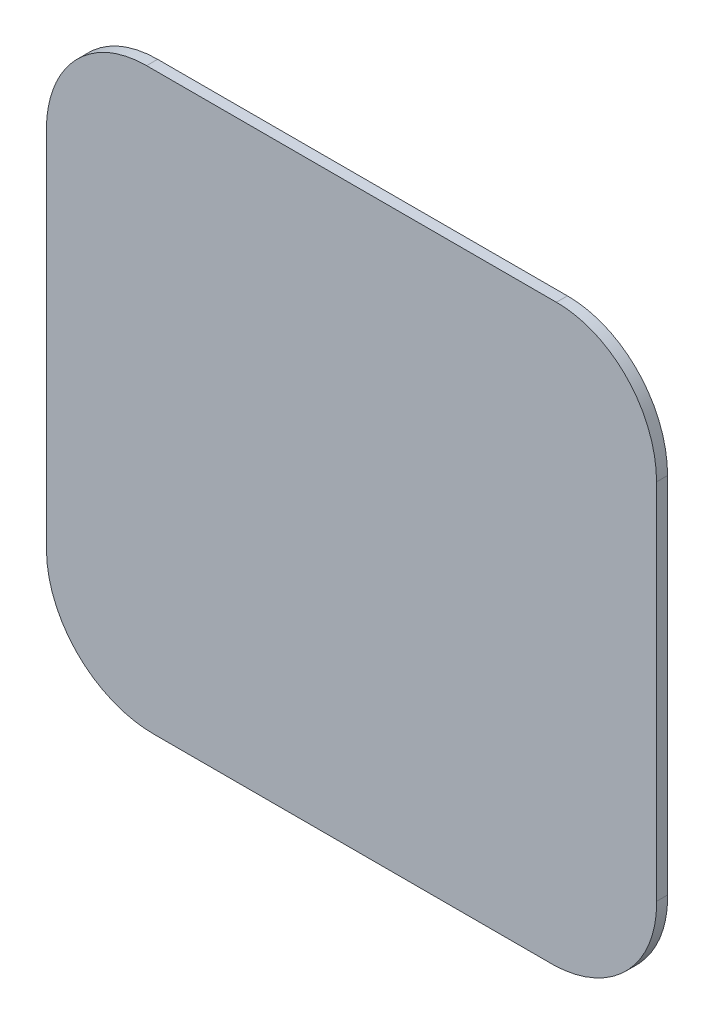
SolidWorks part; units mm, degrees
material "Beech"
ref_plane "Front Plane" through (0, 0, 0) normal (0, 0, 1) x (1, 0, 0)
ref_plane "Top Plane" through (0, 0, 0) normal (0, 1, 0) x (1, 0, 0)
ref_plane "Right Plane" through (0, 0, 0) normal (1, 0, 0) x (0, 0, -1)
sketch "Sketch1" plane through (0, 0, 0) normal (0, 0, 1) x (1, 0, 0)
  line L0 (-105.3184, 124.9067) -> (-105.3184, -72.5)
  line L1 (-105.3184, -72.5) -> (103.4563, -72.5)
  line L2 (103.4563, -72.5) -> (103.4563, 124.9067)
  line L3 (103.4563, 124.9067) -> (-105.3184, 124.9067)
  line L4 (-80, 72.5) -> (-80, -72.5)
  line L5 (-80, -72.5) -> (80, -72.5)
  line L6 (80, -72.5) -> (80, 72.5)
  line L7 (80, 72.5) -> (-80, 72.5)
  line L8 (-80, 72.5) -> (-80, -72.5) construction
  line L9 (-80, -72.5) -> (80, -72.5) construction
  line L10 (80, -72.5) -> (80, 72.5) construction
  point P25 (-25, 60.7089)
  dimension "D1" = 0
extrude "Boss-Extrude1" add sketch "Sketch1" along normal blind 3
sketch3d "3DSketch1"
  line L0 (-83, -42.5, 2.9036) -> (-83, 56.327, 2.9036)
  line L1 (-83, -42.5, 2.9036) -> (-83, 56.327, 2.9036)
  line L2 (55.7409, 85.0317, 3) -> (-55.7409, 85.0317, 3)
  line L3 (55.7409, 85.0317, 3) -> (-55.7409, 85.0317, 3)
  line L4 (83, 56.327, 2.9036) -> (83, -42.5, 2.9036)
  line L5 (83, 56.327, 2.9036) -> (83, -42.5, 2.9036)
  line L7 (-57.4005, -70.3847, 3) -> (54.8473, -71.5, 2.965)
  spline S0 degree 3 poles (845.7378, -314.4009, 3.5223) (143.8658, -123.3345, 2.8787) (-95.3665, -9.6791, 2.7552) (-82.3503, 62.6938, 2.9171) (-82.1487, 63.5851, 2.9192) (-81.784, 64.9117, 2.9223) (-81.6521, 65.3522, 2.9234) (-81.367, 66.2295, 2.9256) (-81.2136, 66.667, 2.9266) (-80.4005, 68.822, 2.9321) (-79.5995, 70.4619, 2.9365) (-78.1712, 72.7951, 2.9432) (-77.657, 73.5515, 2.9454) (-76.5492, 75.02, 2.9499) (-75.9532, 75.7339, 2.9522) (-74.0842, 77.7574, 2.9589) (-72.7199, 78.9671, 2.9633) (-70.4933, 80.5694, 2.9697) (-69.7201, 81.0683, 2.9718) (-68.1133, 81.9895, 2.976) (-67.2931, 82.4042, 2.978) (-64.7838, 83.5145, 2.9838) (-63.0463, 84.0777, 2.9875) (-60.7916, 84.5546, 2.9917) (-60.3354, 84.6387, 2.9925) (-59.4217, 84.7823, 2.9942) (-58.9638, 84.842, 2.9949) (15.669, 92.5958, 3.1188) (114.6789, -213.0937, 2.6588) (241.5021, -869.7537, 1.5457) knots -4.849351 -4.849351 -4.849351 -4.849351 0.125 0.125 0.1875 0.1875 0.21875 0.21875 0.25 0.25 0.375 0.375 0.4375 0.4375 0.5 0.5 0.625 0.625 0.6875 0.6875 0.75 0.75 0.875 0.875 0.90625 0.90625 0.9375 0.9375 5.989732 5.989732 5.989732 5.989732 only from (-83, 56.327, 2.9036) to (-55.7409, 85.0317, 3)
  spline S1 degree 3 poles (-83, 56.327, 2.9036) (-82.9987, 58.1769, 2.9073) (-82.8348, 59.9997, 2.9111) (-82.3503, 62.6938, 2.9171) (-82.1487, 63.5851, 2.9192) (-81.784, 64.9117, 2.9223) (-81.6521, 65.3522, 2.9234) (-81.367, 66.2295, 2.9256) (-81.2136, 66.667, 2.9266) (-80.4005, 68.822, 2.9321) (-79.5995, 70.4619, 2.9365) (-78.1712, 72.7951, 2.9432) (-77.657, 73.5515, 2.9454) (-76.5492, 75.02, 2.9499) (-75.9532, 75.7339, 2.9522) (-74.0842, 77.7574, 2.9589) (-72.7199, 78.9671, 2.9633) (-70.4933, 80.5694, 2.9697) (-69.7201, 81.0683, 2.9718) (-68.1133, 81.9895, 2.976) (-67.2931, 82.4042, 2.978) (-64.7838, 83.5145, 2.9838) (-63.0463, 84.0777, 2.9875) (-60.7916, 84.5546, 2.9917) (-60.3354, 84.6387, 2.9925) (-59.4217, 84.7823, 2.9942) (-58.9638, 84.842, 2.9949) (-57.5875, 84.985, 2.9972) (-56.6661, 85.0324, 2.9987) (-55.7409, 85.0317, 3) knots 0 0 0 0 0.125 0.125 0.1875 0.1875 0.21875 0.21875 0.25 0.25 0.375 0.375 0.4375 0.4375 0.5 0.5 0.625 0.625 0.6875 0.6875 0.75 0.75 0.875 0.875 0.90625 0.90625 0.9375 0.9375 1 1 1 1
  spline S2 degree 3 poles (-289.6468, -853.4257, 2.481) (-113.5107, -151.129, 3.0446) (-6.1225, 98.5754, 3.1498) (62.0878, 84.2822, 2.9855) (62.9752, 84.0478, 2.9833) (64.7352, 83.482, 2.9788) (65.5969, 83.1537, 2.9765) (68.1083, 82.0454, 2.9697) (69.694, 81.1399, 2.9651) (71.5651, 79.7991, 2.9593) (71.9348, 79.5196, 2.9582) (72.6565, 78.9442, 2.9559) (73.0086, 78.6483, 2.9547) (74.0393, 77.7369, 2.9513) (75.3458, 76.4581, 2.9468) (76.5201, 75.0559, 2.9424) (77.6284, 73.592, 2.9381) (78.1517, 72.8251, 2.936) (79.5948, 70.473, 2.9298) (80.3956, 68.831, 2.9259) (81.3669, 66.2625, 2.9204) (81.6523, 65.3878, 2.9186) (82.1438, 63.606, 2.9152) (82.3472, 62.7093, 2.9135) (96.6275, -16.5223, 2.7772) (-193.7163, -136.4345, 3.235) (-848.9704, -306.1858, 4.4029) knots -4.578436 -4.578436 -4.578436 -4.578436 0.125 0.125 0.1875 0.1875 0.25 0.25 0.375 0.375 0.40625 0.40625 0.4375 0.4375 0.5 0.5625 0.5625 0.625 0.625 0.75 0.75 0.8125 0.8125 0.875 0.875 6.300815 6.300815 6.300815 6.300815 only from (55.7409, 85.0317, 3) to (83, 56.327, 2.9036)
  spline S3 degree 3 poles (55.7409, 85.0317, 3) (57.587, 85.033, 2.9961) (59.4043, 84.8445, 2.992) (62.0878, 84.2822, 2.9855) (62.9752, 84.0478, 2.9833) (64.7352, 83.482, 2.9788) (65.5969, 83.1537, 2.9765) (68.1083, 82.0454, 2.9697) (69.694, 81.1399, 2.9651) (71.5651, 79.7991, 2.9593) (71.9348, 79.5196, 2.9582) (72.6565, 78.9442, 2.9559) (73.0086, 78.6483, 2.9547) (74.0393, 77.7369, 2.9513) (75.3458, 76.4581, 2.9468) (76.5201, 75.0559, 2.9424) (77.6284, 73.592, 2.9381) (78.1517, 72.8251, 2.936) (79.5948, 70.473, 2.9298) (80.3956, 68.831, 2.9259) (81.3669, 66.2625, 2.9204) (81.6523, 65.3878, 2.9186) (82.1438, 63.606, 2.9152) (82.3472, 62.7093, 2.9135) (82.835, 60.0024, 2.9089) (82.9987, 58.1758, 2.9061) (83, 56.327, 2.9036) knots 0 0 0 0 0.125 0.125 0.1875 0.1875 0.25 0.25 0.375 0.375 0.40625 0.40625 0.4375 0.4375 0.5 0.5625 0.5625 0.625 0.625 0.75 0.75 0.8125 0.8125 0.875 0.875 1 1 1 1
  spline S4 degree 3 poles (-859.369, 292.0653, 3.8986) (-111.276, 112.4573, 3.039) (94.1422, 15.6372, 2.8415) (82.379, -48.9917, 2.9097) (82.1672, -49.9003, 2.9107) (81.6513, -51.7035, 2.9129) (81.3458, -52.6, 2.914) (80.3098, -55.2097, 2.9175) (79.4565, -56.863, 2.92) (78.1883, -58.8226, 2.9233) (77.9245, -59.2091, 2.924) (77.3763, -59.9711, 2.9253) (77.091, -60.3477, 2.926) (76.2109, -61.4513, 2.9281) (75.5923, -62.1525, 2.9295) (73.6439, -64.156, 2.9337) (72.2222, -65.3588, 2.9366) (70.2881, -66.6925, 2.9403) (69.8925, -66.9512, 2.9411) (69.0933, -67.446, 2.9425) (68.6891, -67.6828, 2.9433) (67.4627, -68.3614, 2.9455) (65.791, -69.1824, 2.9484) (64.0474, -69.838, 2.9512) (62.7124, -70.267, 2.9534) (62.2628, -70.3994, 2.9541) (61.3544, -70.643, 2.9555) (60.8951, -70.7542, 2.9562) (-14.1598, -86.9814, 3.0702) (-127.8298, 195.8272, 2.9937) (-292.1789, 866.3485, 2.6708) knots -4.224634 -4.224634 -4.224634 -4.224634 0.125 0.125 0.1875 0.1875 0.25 0.25 0.375 0.375 0.40625 0.40625 0.4375 0.4375 0.5 0.5 0.625 0.625 0.65625 0.65625 0.6875 0.6875 0.75 0.8125 0.8125 0.84375 0.84375 0.875 0.875 5.945598 5.945598 5.945598 5.945598 only from (83, -42.5, 2.9036) to (54.8473, -71.5, 2.965)
  spline S5 degree 3 poles (83, -42.5, 2.9036) (83.0329, -44.3869, 2.9051) (82.8789, -46.2452, 2.9068) (82.379, -48.9917, 2.9097) (82.1672, -49.9003, 2.9107) (81.6513, -51.7035, 2.9129) (81.3458, -52.6, 2.914) (80.3098, -55.2097, 2.9175) (79.4565, -56.863, 2.92) (78.1883, -58.8226, 2.9233) (77.9245, -59.2091, 2.924) (77.3763, -59.9711, 2.9253) (77.091, -60.3477, 2.926) (76.2109, -61.4513, 2.9281) (75.5923, -62.1525, 2.9295) (73.6439, -64.156, 2.9337) (72.2222, -65.3588, 2.9366) (70.2881, -66.6925, 2.9403) (69.8925, -66.9512, 2.9411) (69.0933, -67.446, 2.9425) (68.6891, -67.6828, 2.9433) (67.4627, -68.3614, 2.9455) (65.791, -69.1824, 2.9484) (64.0474, -69.838, 2.9512) (62.7124, -70.267, 2.9534) (62.2628, -70.3994, 2.9541) (61.3544, -70.643, 2.9555) (60.8951, -70.7542, 2.9562) (58.5965, -71.2512, 2.9597) (56.7338, -71.4671, 2.9624) (54.8473, -71.5, 2.965) knots 0 0 0 0 0.125 0.125 0.1875 0.1875 0.25 0.25 0.375 0.375 0.40625 0.40625 0.4375 0.4375 0.5 0.5 0.625 0.625 0.65625 0.65625 0.6875 0.6875 0.75 0.8125 0.8125 0.84375 0.84375 0.875 0.875 1 1 1 1
  spline S6 degree 3 poles (854.0596, 306.6892, 3) (108.2999, 114.5623, 3) (-95.0277, 14.8956, 3) (-82.2695, -48.8652, 3) (-82.0459, -49.754, 3) (-81.5083, -51.5161, 3) (-81.1929, -52.3914, 3) (-80.1307, -54.9368, 3) (-79.2642, -56.5459, 3) (-77.9851, -58.4488, 3) (-77.7194, -58.8239, 3) (-77.1679, -59.5629, 3) (-76.8813, -59.9279, 3) (-75.998, -60.9967, 3) (-75.3784, -61.6748, 3) (-73.4304, -63.6091, 3) (-72.0135, -64.7661, 3) (-70.0911, -66.0429, 3) (-69.6981, -66.2902, 3) (-68.9047, -66.7625, 3) (-68.5036, -66.9881, 3) (-67.2875, -67.6336, 3) (-65.6316, -68.4113, 3) (-63.9079, -69.0253, 3) (-62.5893, -69.4237, 3) (-62.1455, -69.5461, 3) (-61.2491, -69.7698, 3) (-60.7962, -69.8711, 3) (13.8382, -84.6496, 3) (121.8565, 200.0841, 3) (273.8484, 873.9357, 3) knots -4.258592 -4.258592 -4.258592 -4.258592 0.125 0.125 0.1875 0.1875 0.25 0.25 0.375 0.375 0.40625 0.40625 0.4375 0.4375 0.5 0.5 0.625 0.625 0.65625 0.65625 0.6875 0.6875 0.75 0.8125 0.8125 0.84375 0.84375 0.875 0.875 5.989794 5.989794 5.989794 5.989794 only from (-82.9907, -42.5, 3) to (-54.8435, -70.5, 3)
  spline S7 degree 3 poles (-82.9907, -42.5, 3) (-82.9907, -44.3537, 3) (-82.8075, -46.1763, 3) (-82.2695, -48.8652, 3) (-82.0459, -49.754, 3) (-81.5083, -51.5161, 3) (-81.1929, -52.3914, 3) (-80.1307, -54.9368, 3) (-79.2642, -56.5459, 3) (-77.9851, -58.4488, 3) (-77.7194, -58.8239, 3) (-77.1679, -59.5629, 3) (-76.8813, -59.9279, 3) (-75.998, -60.9967, 3) (-75.3784, -61.6748, 3) (-73.4304, -63.6091, 3) (-72.0135, -64.7661, 3) (-70.0911, -66.0429, 3) (-69.6981, -66.2902, 3) (-68.9047, -66.7625, 3) (-68.5036, -66.9881, 3) (-67.2875, -67.6336, 3) (-65.6316, -68.4113, 3) (-63.9079, -69.0253, 3) (-62.5893, -69.4237, 3) (-62.1455, -69.5461, 3) (-61.2491, -69.7698, 3) (-60.7962, -69.8711, 3) (-59.368, -70.1539, 3) (-58.3872, -70.2953, 3) (-57.4005, -70.3847, 3) knots 0 0 0 0 0.125 0.125 0.1875 0.1875 0.25 0.25 0.375 0.375 0.40625 0.40625 0.4375 0.4375 0.5 0.5 0.625 0.625 0.65625 0.65625 0.6875 0.6875 0.75 0.8125 0.8125 0.84375 0.84375 0.875 0.875 0.942224 0.942224 0.942224 0.942224
sketch "Sketch3" plane through (0, 0, 3) normal (0, 0, 1) x (1, 0, 0)
  line L0 (-83, -42.5) -> (-83, 56.327) construction
  line L1 (83, 56.327) -> (83, -42.5) construction
  line L2 (55.7409, 85.0317) -> (-55.7409, 85.0317) construction
  line L3 (-83, -42.5) -> (-83, 56.327)
  line L4 (83, 56.327) -> (83, -42.5)
  line L5 (55.7409, 85.0317) -> (-55.7409, 85.0317)
  line L6 (-53.847, -71.5) -> (54.8473, -71.5)
  spline S0 degree 3 poles (-859.369, 292.0653) (-111.276, 112.4573) (94.1422, 15.6372) (82.379, -48.9917) (82.1672, -49.9003) (81.6513, -51.7035) (81.3458, -52.6) (80.3098, -55.2097) (79.4565, -56.863) (78.1883, -58.8226) (77.9245, -59.2091) (77.3763, -59.9711) (77.091, -60.3477) (76.2109, -61.4513) (75.5923, -62.1525) (73.6439, -64.156) (72.2222, -65.3588) (70.2881, -66.6925) (69.8925, -66.9512) (69.0933, -67.446) (68.6891, -67.6828) (67.4627, -68.3614) (65.791, -69.1824) (64.0474, -69.838) (62.7124, -70.267) (62.2628, -70.3994) (61.3544, -70.643) (60.8951, -70.7542) (-14.1598, -86.9814) (-127.8298, 195.8272) (-292.1789, 866.3485) knots -4.224634 -4.224634 -4.224634 -4.224634 0.125 0.125 0.1875 0.1875 0.25 0.25 0.375 0.375 0.40625 0.40625 0.4375 0.4375 0.5 0.5 0.625 0.625 0.65625 0.65625 0.6875 0.6875 0.75 0.8125 0.8125 0.84375 0.84375 0.875 0.875 5.945598 5.945598 5.945598 5.945598 only from (83, -42.5) to (54.8473, -71.5) construction
  spline S2 degree 3 poles (-289.6468, -853.4257) (-113.5107, -151.129) (-6.1225, 98.5754) (62.0878, 84.2822) (62.9752, 84.0478) (64.7352, 83.482) (65.5969, 83.1537) (68.1083, 82.0454) (69.694, 81.1399) (71.5651, 79.7991) (71.9348, 79.5196) (72.6565, 78.9442) (73.0086, 78.6483) (74.0393, 77.7369) (75.3458, 76.4581) (76.5201, 75.0559) (77.6284, 73.592) (78.1517, 72.8251) (79.5948, 70.473) (80.3956, 68.831) (81.3669, 66.2625) (81.6523, 65.3878) (82.1438, 63.606) (82.3472, 62.7093) (96.6275, -16.5223) (-193.7163, -136.4345) (-848.9704, -306.1858) knots -4.578436 -4.578436 -4.578436 -4.578436 0.125 0.125 0.1875 0.1875 0.25 0.25 0.375 0.375 0.40625 0.40625 0.4375 0.4375 0.5 0.5625 0.5625 0.625 0.625 0.75 0.75 0.8125 0.8125 0.875 0.875 6.300815 6.300815 6.300815 6.300815 only from (55.7409, 85.0317) to (83, 56.327) construction
  spline S3 degree 3 poles (845.741, -314.4018) (143.8665, -123.3348) (-95.3666, -9.6792) (-82.3503, 62.6938) (-82.1487, 63.5851) (-81.784, 64.9117) (-81.6521, 65.3522) (-81.367, 66.2295) (-81.2136, 66.667) (-80.4005, 68.822) (-79.5995, 70.4619) (-78.1712, 72.7951) (-77.657, 73.5515) (-76.5492, 75.02) (-75.9532, 75.7339) (-74.0842, 77.7574) (-72.7199, 78.9671) (-70.4933, 80.5694) (-69.7201, 81.0683) (-68.1133, 81.9895) (-67.2931, 82.4042) (-64.7838, 83.5145) (-63.0463, 84.0777) (-60.7916, 84.5546) (-60.3354, 84.6387) (-59.4217, 84.7823) (-58.9638, 84.842) (15.6691, 92.5959) (114.6791, -213.0945) (241.5026, -869.7563) knots -4.849358 -4.849358 -4.849358 -4.849358 0.125 0.125 0.1875 0.1875 0.21875 0.21875 0.25 0.25 0.375 0.375 0.4375 0.4375 0.5 0.5 0.625 0.625 0.6875 0.6875 0.75 0.75 0.875 0.875 0.90625 0.90625 0.9375 0.9375 5.989738 5.989738 5.989738 5.989738 only from (-83, 56.327) to (-55.7409, 85.0317) construction
  spline S4 degree 3 poles (83, -42.5) (83.0329, -44.3869) (82.8789, -46.2452) (82.379, -48.9917) (82.1672, -49.9003) (81.6513, -51.7035) (81.3458, -52.6) (80.3098, -55.2097) (79.4565, -56.863) (78.1883, -58.8226) (77.9245, -59.2091) (77.3763, -59.9711) (77.091, -60.3477) (76.2109, -61.4513) (75.5923, -62.1525) (73.6439, -64.156) (72.2222, -65.3588) (70.2881, -66.6925) (69.8925, -66.9512) (69.0933, -67.446) (68.6891, -67.6828) (67.4627, -68.3614) (65.791, -69.1824) (64.0474, -69.838) (62.7124, -70.267) (62.2628, -70.3994) (61.3544, -70.643) (60.8951, -70.7542) (58.5965, -71.2512) (56.7338, -71.4671) (54.8473, -71.5) knots 0 0 0 0 0.125 0.125 0.1875 0.1875 0.25 0.25 0.375 0.375 0.40625 0.40625 0.4375 0.4375 0.5 0.5 0.625 0.625 0.65625 0.65625 0.6875 0.6875 0.75 0.8125 0.8125 0.84375 0.84375 0.875 0.875 1 1 1 1
  spline S5 degree 3 poles (-83, -42.5) (-83, -44.42) (-82.8103, -46.3076) (-82.253, -49.0926) (-82.0215, -50.0131) (-81.4647, -51.8381) (-81.138, -52.7447) (-80.0378, -55.381) (-79.1403, -57.0477) (-77.8155, -59.0185) (-77.5403, -59.4069) (-76.9691, -60.1724) (-76.6722, -60.5504) (-75.7573, -61.6574) (-75.1156, -62.3597) (-73.098, -64.3631) (-71.6304, -65.5614) (-69.6393, -66.8837) (-69.2323, -67.1398) (-68.4106, -67.629) (-67.9952, -67.8626) (-66.7356, -68.5312) (-65.0205, -69.3367) (-63.2352, -69.9727) (-61.8695, -70.3853) (-61.4099, -70.5121) (-60.4815, -70.7438) (-60.0123, -70.8487) (-57.6653, -71.3134) (-55.7667, -71.5) (-53.847, -71.5) knots 0 0 0 0 0.125 0.125 0.1875 0.1875 0.25 0.25 0.375 0.375 0.40625 0.40625 0.4375 0.4375 0.5 0.5 0.625 0.625 0.65625 0.65625 0.6875 0.6875 0.75 0.8125 0.8125 0.84375 0.84375 0.875 0.875 1 1 1 1
  spline S6 degree 3 poles (55.7409, 85.0317) (57.587, 85.033) (59.4043, 84.8445) (62.0878, 84.2822) (62.9752, 84.0478) (64.7352, 83.482) (65.5969, 83.1537) (68.1083, 82.0454) (69.694, 81.1399) (71.5651, 79.7991) (71.9348, 79.5196) (72.6565, 78.9442) (73.0086, 78.6483) (74.0393, 77.7369) (75.3458, 76.4581) (76.5201, 75.0559) (77.6284, 73.592) (78.1517, 72.8251) (79.5948, 70.473) (80.3956, 68.831) (81.3669, 66.2625) (81.6523, 65.3878) (82.1438, 63.606) (82.3472, 62.7093) (82.835, 60.0024) (82.9987, 58.1758) (83, 56.327) knots 0 0 0 0 0.125 0.125 0.1875 0.1875 0.25 0.25 0.375 0.375 0.40625 0.40625 0.4375 0.4375 0.5 0.5625 0.5625 0.625 0.625 0.75 0.75 0.8125 0.8125 0.875 0.875 1 1 1 1
  spline S7 degree 3 poles (-83, 56.327) (-82.9987, 58.1769) (-82.8348, 59.9997) (-82.3503, 62.6938) (-82.1487, 63.5851) (-81.784, 64.9117) (-81.6521, 65.3522) (-81.367, 66.2295) (-81.2136, 66.667) (-80.4005, 68.822) (-79.5995, 70.4619) (-78.1712, 72.7951) (-77.657, 73.5515) (-76.5492, 75.02) (-75.9532, 75.7339) (-74.0842, 77.7574) (-72.7199, 78.9671) (-70.4933, 80.5694) (-69.7201, 81.0683) (-68.1133, 81.9895) (-67.2931, 82.4042) (-64.7838, 83.5145) (-63.0463, 84.0777) (-60.7916, 84.5546) (-60.3354, 84.6387) (-59.4217, 84.7823) (-58.9638, 84.842) (-57.5875, 84.985) (-56.6661, 85.0324) (-55.7409, 85.0317) knots 0 0 0 0 0.125 0.125 0.1875 0.1875 0.21875 0.21875 0.25 0.25 0.375 0.375 0.4375 0.4375 0.5 0.5 0.625 0.625 0.6875 0.6875 0.75 0.75 0.875 0.875 0.90625 0.90625 0.9375 0.9375 1 1 1 1
extrude "Cut-Extrude1" cut sketch "Sketch3" against normal through all both and the other way through all flip side to cut
